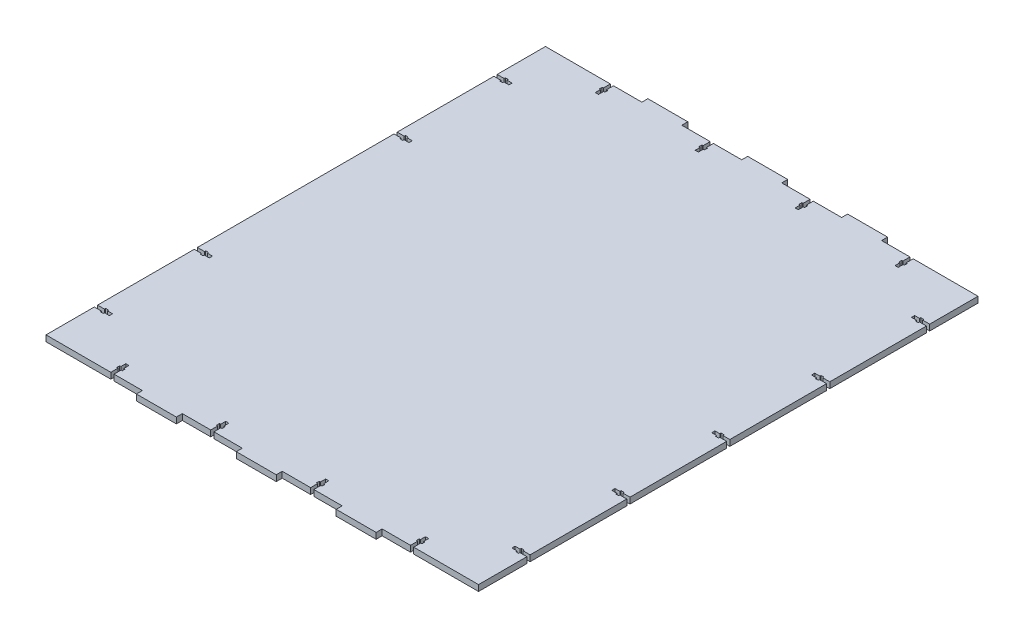
SolidWorks part; units mm, degrees
ref_plane "Front Plane" through (0, 0, 0) normal (0, 0, 1) x (1, 0, 0)
ref_plane "Top Plane" through (0, 0, 0) normal (0, 1, 0) x (1, 0, 0)
ref_plane "Right Plane" through (0, 0, 0) normal (1, 0, 0) x (0, 0, -1)
sketch "Sketch1" plane through (0, 0, 0) normal (0, 1, 0) x (1, 0, 0)
  line L1 (-216.5, -250) -> (216.5, -250)
  line L2 (-216.5, -250) -> (-216.5, 250)
  line L3 (-216.5, 250) -> (216.5, 250)
  line L4 (216.5, -250) -> (216.5, 250)
  line L5 (-216.5, -250) -> (216.5, 250) construction
  line L6 (-216.5, 250) -> (216.5, -250) construction
  point P0 (0, 0)
  dimension "D1" = 433
  dimension "D2" = 500
extrude "Boss-Extrude1" add sketch "Sketch1" along normal blind 6
sketch "Sketch2" plane through (0, 0, 0) normal (0, -1, 0) x (1, 0, 0)
  line L14 (0, 0) -> (0, 133.2527) construction
  line L15 (0, 0) -> (-145.1849, 0) construction
  line L40 (-148.4, 256) -> (-151.6, 256) construction
  line L41 (-148.4, 256) -> (-151.6, 256) construction
  line L42 (-48.4, 256) -> (-51.6, 256) construction
  line L43 (-48.4, 256) -> (-51.6, 256) construction
  line L44 (-148.4, 256) -> (-51.6, 256) construction
  line L45 (-216.5, 250) -> (216.5, 250) construction
  line L46 (-120, 256) -> (-80, 256)
  line L47 (-120, 256) -> (-120, 250)
  line L48 (-120, 250) -> (-80, 250)
  line L49 (-80, 256) -> (-80, 250)
  line L50 (-20, 250) -> (20, 250)
  line L51 (20, 256) -> (20, 250)
  line L52 (-20, 256) -> (20, 256)
  line L53 (-20, 256) -> (-20, 250)
  line L54 (80, 250) -> (120, 250)
  line L55 (120, 256) -> (120, 250)
  line L56 (80, 256) -> (120, 256)
  line L57 (80, 256) -> (80, 250)
  line L58 (120, -256) -> (120, -250)
  line L59 (80, -250) -> (120, -250)
  line L60 (80, -256) -> (120, -256)
  line L61 (80, -256) -> (80, -250)
  line L62 (20, -256) -> (20, -250)
  line L63 (-20, -256) -> (20, -256)
  line L64 (-20, -250) -> (20, -250)
  line L65 (-20, -256) -> (-20, -250)
  line L66 (-120, -250) -> (-80, -250)
  line L67 (-120, -256) -> (-120, -250)
  line L68 (-120, -256) -> (-80, -256)
  line L69 (-80, -256) -> (-80, -250)
  point P50 (-100, 256)
  dimension "D3" = 40
  dimension "D4" = 3
extrude "Boss-Extrude2" add sketch "Sketch2" against normal blind 6
sketch "Sketch3" plane through (0, 0, 0) normal (0, -1, 0) x (1, 0, 0)
  line L0 (-222.5, -198.4) -> (-222.5, -201.6) construction
  line L1 (-222.5, -198.4) -> (-222.5, -201.6)
  line L2 (-222.5, -200) -> (-193.4637, -200) construction
  line L3 (-216.5, -250) -> (-216.5, 250) construction
  line L4 (-201.5, -201.6) -> (-206.5, -201.6)
  line L5 (-201.5, -201.6) -> (-201.5, -198.4)
  line L6 (-201.5, -198.4) -> (-206.5, -198.4)
  line L7 (-216.5, -201.6) -> (-216.5, -198.4)
  line L8 (-201.5, -201.6) -> (-216.5, -198.4) construction
  line L9 (-201.5, -198.4) -> (-216.5, -201.6) construction
  line L10 (-209.5, -198.4) -> (-216.5, -198.4)
  line L11 (-206.5, -202.8) -> (-209.5, -202.8)
  line L12 (-206.5, -202.8) -> (-206.5, -201.6)
  line L13 (-206.5, -197.2) -> (-209.5, -197.2)
  line L14 (-209.5, -202.8) -> (-209.5, -201.6)
  line L15 (-206.5, -202.8) -> (-209.5, -197.2) construction
  line L16 (-206.5, -197.2) -> (-209.5, -202.8) construction
  line L17 (-209.5, -201.6) -> (-216.5, -201.6)
  line L18 (-201.5, -101.6) -> (-206.5, -101.6)
  line L19 (-209.5, -198.4) -> (-209.5, -197.2)
  line L20 (-206.5, -198.4) -> (-206.5, -197.2)
  line L21 (206.5, 202.8) -> (209.5, 197.2) construction
  line L22 (-201.5, -101.6) -> (-201.5, -98.4)
  line L24 (-201.5, -98.4) -> (-206.5, -98.4)
  line L25 (-216.5, -101.6) -> (-216.5, -98.4)
  line L26 (-209.5, -98.4) -> (-216.5, -98.4)
  line L27 (-206.5, -102.8) -> (-209.5, -102.8)
  line L28 (-206.5, -102.8) -> (-206.5, -101.6)
  line L29 (-206.5, -97.2) -> (-209.5, -97.2)
  line L30 (-209.5, -102.8) -> (-209.5, -101.6)
  line L31 (-209.5, -101.6) -> (-216.5, -101.6)
  line L32 (-209.5, -98.4) -> (-209.5, -97.2)
  line L33 (-206.5, -98.4) -> (-206.5, -97.2)
  line L34 (-201.5, -101.6) -> (-216.5, -98.4) construction
  line L35 (-201.5, -98.4) -> (-216.5, -101.6) construction
  line L36 (-206.5, -102.8) -> (-209.5, -97.2) construction
  line L37 (-206.5, -97.2) -> (-209.5, -102.8) construction
  line L38 (-201.5, -1.6) -> (-206.5, -1.6)
  line L39 (-201.5, -1.6) -> (-201.5, 1.6)
  line L40 (-201.5, 1.6) -> (-206.5, 1.6)
  line L41 (-216.5, -1.6) -> (-216.5, 1.6)
  line L42 (-209.5, 1.6) -> (-216.5, 1.6)
  line L43 (-206.5, -2.8) -> (-209.5, -2.8)
  line L44 (-206.5, -2.8) -> (-206.5, -1.6)
  line L45 (-206.5, 2.8) -> (-209.5, 2.8)
  line L46 (-209.5, -2.8) -> (-209.5, -1.6)
  line L47 (-209.5, -1.6) -> (-216.5, -1.6)
  line L48 (-209.5, 1.6) -> (-209.5, 2.8)
  line L49 (-206.5, 1.6) -> (-206.5, 2.8)
  line L50 (-201.5, -1.6) -> (-216.5, 1.6) construction
  line L51 (-201.5, 1.6) -> (-216.5, -1.6) construction
  line L52 (-206.5, -2.8) -> (-209.5, 2.8) construction
  line L53 (-206.5, 2.8) -> (-209.5, -2.8) construction
  line L54 (-201.5, 98.4) -> (-206.5, 98.4)
  line L55 (-201.5, 98.4) -> (-201.5, 101.6)
  line L56 (-201.5, 101.6) -> (-206.5, 101.6)
  line L57 (-216.5, 98.4) -> (-216.5, 101.6)
  line L58 (-209.5, 101.6) -> (-216.5, 101.6)
  line L59 (-206.5, 97.2) -> (-209.5, 97.2)
  line L60 (-206.5, 97.2) -> (-206.5, 98.4)
  line L61 (-206.5, 102.8) -> (-209.5, 102.8)
  line L62 (-209.5, 97.2) -> (-209.5, 98.4)
  line L63 (-209.5, 98.4) -> (-216.5, 98.4)
  line L64 (-209.5, 101.6) -> (-209.5, 102.8)
  line L65 (-206.5, 101.6) -> (-206.5, 102.8)
  line L66 (-201.5, 98.4) -> (-216.5, 101.6) construction
  line L67 (-201.5, 101.6) -> (-216.5, 98.4) construction
  line L68 (-206.5, 97.2) -> (-209.5, 102.8) construction
  line L69 (-206.5, 102.8) -> (-209.5, 97.2) construction
  line L70 (-201.5, 198.4) -> (-206.5, 198.4)
  line L71 (-201.5, 198.4) -> (-201.5, 201.6)
  line L72 (-201.5, 201.6) -> (-206.5, 201.6)
  line L73 (-216.5, 198.4) -> (-216.5, 201.6)
  line L74 (-209.5, 201.6) -> (-216.5, 201.6)
  line L75 (-206.5, 197.2) -> (-209.5, 197.2)
  line L76 (-206.5, 197.2) -> (-206.5, 198.4)
  line L77 (-206.5, 202.8) -> (-209.5, 202.8)
  line L78 (-209.5, 197.2) -> (-209.5, 198.4)
  line L79 (-209.5, 198.4) -> (-216.5, 198.4)
  line L80 (-209.5, 201.6) -> (-209.5, 202.8)
  line L81 (-206.5, 201.6) -> (-206.5, 202.8)
  line L82 (-201.5, 198.4) -> (-216.5, 201.6) construction
  line L83 (-201.5, 201.6) -> (-216.5, 198.4) construction
  line L84 (-206.5, 197.2) -> (-209.5, 202.8) construction
  line L85 (-206.5, 202.8) -> (-209.5, 197.2) construction
  line L86 (0, 0) -> (0, 128.8409) construction
  line L87 (206.5, 197.2) -> (209.5, 202.8) construction
  line L88 (201.5, 201.6) -> (216.5, 198.4) construction
  line L89 (201.5, 198.4) -> (216.5, 201.6) construction
  line L90 (206.5, 102.8) -> (209.5, 97.2) construction
  line L91 (206.5, 97.2) -> (209.5, 102.8) construction
  line L92 (201.5, 101.6) -> (216.5, 98.4) construction
  line L93 (201.5, 98.4) -> (216.5, 101.6) construction
  line L94 (206.5, 2.8) -> (209.5, -2.8) construction
  line L95 (206.5, -2.8) -> (209.5, 2.8) construction
  line L96 (201.5, 1.6) -> (216.5, -1.6) construction
  line L97 (201.5, -1.6) -> (216.5, 1.6) construction
  line L98 (206.5, -97.2) -> (209.5, -102.8) construction
  line L99 (206.5, -102.8) -> (209.5, -97.2) construction
  line L100 (201.5, -98.4) -> (216.5, -101.6) construction
  line L101 (201.5, -101.6) -> (216.5, -98.4) construction
  line L102 (206.5, -197.2) -> (209.5, -202.8) construction
  line L103 (206.5, -202.8) -> (209.5, -197.2) construction
  line L104 (201.5, -198.4) -> (216.5, -201.6) construction
  line L105 (201.5, -201.6) -> (216.5, -198.4) construction
  line L106 (206.5, 201.6) -> (206.5, 202.8)
  line L107 (209.5, 201.6) -> (209.5, 202.8)
  line L108 (209.5, 198.4) -> (216.5, 198.4)
  line L109 (209.5, 197.2) -> (209.5, 198.4)
  line L110 (206.5, 202.8) -> (209.5, 202.8)
  line L111 (206.5, 197.2) -> (206.5, 198.4)
  line L112 (206.5, 197.2) -> (209.5, 197.2)
  line L113 (209.5, 201.6) -> (216.5, 201.6)
  line L114 (216.5, 198.4) -> (216.5, 201.6)
  line L115 (201.5, 201.6) -> (206.5, 201.6)
  line L116 (201.5, 198.4) -> (201.5, 201.6)
  line L117 (201.5, 198.4) -> (206.5, 198.4)
  line L118 (206.5, 101.6) -> (206.5, 102.8)
  line L119 (209.5, 101.6) -> (209.5, 102.8)
  line L120 (209.5, 98.4) -> (216.5, 98.4)
  line L121 (209.5, 97.2) -> (209.5, 98.4)
  line L122 (206.5, 102.8) -> (209.5, 102.8)
  line L123 (206.5, 97.2) -> (206.5, 98.4)
  line L124 (206.5, 97.2) -> (209.5, 97.2)
  line L125 (209.5, 101.6) -> (216.5, 101.6)
  line L126 (216.5, 98.4) -> (216.5, 101.6)
  line L127 (201.5, 101.6) -> (206.5, 101.6)
  line L128 (201.5, 98.4) -> (201.5, 101.6)
  line L129 (201.5, 98.4) -> (206.5, 98.4)
  line L130 (206.5, 1.6) -> (206.5, 2.8)
  line L131 (209.5, 1.6) -> (209.5, 2.8)
  line L132 (209.5, -1.6) -> (216.5, -1.6)
  line L133 (209.5, -2.8) -> (209.5, -1.6)
  line L134 (206.5, 2.8) -> (209.5, 2.8)
  line L135 (206.5, -2.8) -> (206.5, -1.6)
  line L136 (206.5, -2.8) -> (209.5, -2.8)
  line L137 (209.5, 1.6) -> (216.5, 1.6)
  line L138 (216.5, -1.6) -> (216.5, 1.6)
  line L139 (201.5, 1.6) -> (206.5, 1.6)
  line L140 (201.5, -1.6) -> (201.5, 1.6)
  line L141 (201.5, -1.6) -> (206.5, -1.6)
  line L142 (206.5, -98.4) -> (206.5, -97.2)
  line L143 (209.5, -98.4) -> (209.5, -97.2)
  line L144 (209.5, -101.6) -> (216.5, -101.6)
  line L145 (209.5, -102.8) -> (209.5, -101.6)
  line L146 (206.5, -97.2) -> (209.5, -97.2)
  line L147 (206.5, -102.8) -> (206.5, -101.6)
  line L148 (206.5, -102.8) -> (209.5, -102.8)
  line L149 (209.5, -98.4) -> (216.5, -98.4)
  line L150 (216.5, -101.6) -> (216.5, -98.4)
  line L151 (201.5, -98.4) -> (206.5, -98.4)
  line L152 (201.5, -101.6) -> (201.5, -98.4)
  line L153 (206.5, -198.4) -> (206.5, -197.2)
  line L154 (209.5, -198.4) -> (209.5, -197.2)
  line L155 (201.5, -101.6) -> (206.5, -101.6)
  line L156 (209.5, -201.6) -> (216.5, -201.6)
  line L157 (209.5, -202.8) -> (209.5, -201.6)
  line L158 (206.5, -197.2) -> (209.5, -197.2)
  line L159 (206.5, -202.8) -> (206.5, -201.6)
  line L160 (206.5, -202.8) -> (209.5, -202.8)
  line L161 (209.5, -198.4) -> (216.5, -198.4)
  line L162 (216.5, -201.6) -> (216.5, -198.4)
  line L163 (201.5, -198.4) -> (206.5, -198.4)
  line L164 (201.5, -201.6) -> (201.5, -198.4)
  line L165 (201.5, -201.6) -> (206.5, -201.6)
  line L166 (-151.6, -256) -> (-148.4, -256) construction
  line L167 (-151.6, -256) -> (-148.4, -256) construction
  line L168 (-150, -256) -> (-150, -234.6121) construction
  line L169 (-120, -250) -> (-216.5, -250) construction
  line L170 (-151.6, -235) -> (-148.4, -235)
  line L171 (-151.6, -235) -> (-151.6, -240)
  line L172 (-151.6, -250) -> (-148.4, -250)
  line L173 (-148.4, -235) -> (-148.4, -240)
  line L174 (-151.6, -235) -> (-148.4, -250) construction
  line L175 (-151.6, -250) -> (-148.4, -235) construction
  line L176 (-148.4, -243) -> (-147.2, -243)
  line L177 (-152.8, -243) -> (-151.6, -243)
  line L178 (-152.8, -243) -> (-152.8, -240)
  line L179 (-152.8, -240) -> (-151.6, -240)
  line L180 (-147.2, -243) -> (-147.2, -240)
  line L181 (-152.8, -243) -> (-147.2, -240) construction
  line L182 (-152.8, -240) -> (-147.2, -243) construction
  line L183 (-151.6, -243) -> (-151.6, -250)
  line L184 (-148.4, -243) -> (-148.4, -250)
  line L185 (-148.4, -240) -> (-147.2, -240)
  line L186 (-51.6, -235) -> (-48.4, -235)
  line L187 (-51.6, -235) -> (-51.6, -240)
  line L188 (-51.6, -250) -> (-48.4, -250)
  line L189 (-48.4, -235) -> (-48.4, -240)
  line L190 (-48.4, -243) -> (-47.2, -243)
  line L191 (-52.8, -243) -> (-51.6, -243)
  line L192 (-52.8, -243) -> (-52.8, -240)
  line L193 (-52.8, -240) -> (-51.6, -240)
  line L194 (-47.2, -243) -> (-47.2, -240)
  line L195 (-51.6, -243) -> (-51.6, -250)
  line L196 (-48.4, -243) -> (-48.4, -250)
  line L197 (-48.4, -240) -> (-47.2, -240)
  line L198 (-51.6, -235) -> (-48.4, -250) construction
  line L199 (-51.6, -250) -> (-48.4, -235) construction
  line L200 (-52.8, -243) -> (-47.2, -240) construction
  line L201 (-52.8, -240) -> (-47.2, -243) construction
  line L202 (48.4, -235) -> (51.6, -235)
  line L203 (48.4, -235) -> (48.4, -240)
  line L204 (48.4, -250) -> (51.6, -250)
  line L205 (51.6, -235) -> (51.6, -240)
  line L206 (51.6, -243) -> (52.8, -243)
  line L207 (47.2, -243) -> (48.4, -243)
  line L208 (47.2, -243) -> (47.2, -240)
  line L209 (47.2, -240) -> (48.4, -240)
  line L210 (52.8, -243) -> (52.8, -240)
  line L211 (48.4, -243) -> (48.4, -250)
  line L212 (51.6, -243) -> (51.6, -250)
  line L213 (51.6, -240) -> (52.8, -240)
  line L214 (48.4, -235) -> (51.6, -250) construction
  line L215 (48.4, -250) -> (51.6, -235) construction
  line L216 (47.2, -243) -> (52.8, -240) construction
  line L217 (47.2, -240) -> (52.8, -243) construction
  line L218 (148.4, -235) -> (151.6, -235)
  line L219 (148.4, -235) -> (148.4, -240)
  line L220 (148.4, -250) -> (151.6, -250)
  line L221 (151.6, -235) -> (151.6, -240)
  line L222 (151.6, -243) -> (152.8, -243)
  line L223 (147.2, -243) -> (148.4, -243)
  line L224 (147.2, -243) -> (147.2, -240)
  line L225 (147.2, -240) -> (148.4, -240)
  line L226 (152.8, -243) -> (152.8, -240)
  line L227 (148.4, -243) -> (148.4, -250)
  line L228 (151.6, -243) -> (151.6, -250)
  line L229 (151.6, -240) -> (152.8, -240)
  line L230 (148.4, -235) -> (151.6, -250) construction
  line L231 (148.4, -250) -> (151.6, -235) construction
  line L232 (147.2, -243) -> (152.8, -240) construction
  line L233 (147.2, -240) -> (152.8, -243) construction
  line L234 (0, 0) -> (96.8105, 0) construction
  line L235 (147.2, 240) -> (152.8, 243) construction
  line L236 (147.2, 243) -> (152.8, 240) construction
  line L237 (148.4, 250) -> (151.6, 235) construction
  line L238 (148.4, 235) -> (151.6, 250) construction
  line L239 (47.2, 240) -> (52.8, 243) construction
  line L240 (47.2, 243) -> (52.8, 240) construction
  line L241 (48.4, 250) -> (51.6, 235) construction
  line L242 (48.4, 235) -> (51.6, 250) construction
  line L243 (-52.8, 240) -> (-47.2, 243) construction
  line L244 (-52.8, 243) -> (-47.2, 240) construction
  line L245 (-51.6, 250) -> (-48.4, 235) construction
  line L246 (-51.6, 235) -> (-48.4, 250) construction
  line L247 (-152.8, 240) -> (-147.2, 243) construction
  line L248 (-152.8, 243) -> (-147.2, 240) construction
  line L249 (-151.6, 250) -> (-148.4, 235) construction
  line L250 (-151.6, 235) -> (-148.4, 250) construction
  line L251 (151.6, 240) -> (152.8, 240)
  line L252 (151.6, 243) -> (151.6, 250)
  line L253 (148.4, 243) -> (148.4, 250)
  line L254 (152.8, 243) -> (152.8, 240)
  line L255 (147.2, 240) -> (148.4, 240)
  line L256 (147.2, 243) -> (147.2, 240)
  line L257 (147.2, 243) -> (148.4, 243)
  line L258 (151.6, 243) -> (152.8, 243)
  line L259 (151.6, 235) -> (151.6, 240)
  line L260 (148.4, 250) -> (151.6, 250)
  line L261 (148.4, 235) -> (148.4, 240)
  line L262 (148.4, 235) -> (151.6, 235)
  line L263 (51.6, 240) -> (52.8, 240)
  line L264 (51.6, 243) -> (51.6, 250)
  line L265 (48.4, 243) -> (48.4, 250)
  line L266 (52.8, 243) -> (52.8, 240)
  line L267 (47.2, 240) -> (48.4, 240)
  line L268 (47.2, 243) -> (47.2, 240)
  line L269 (47.2, 243) -> (48.4, 243)
  line L270 (51.6, 243) -> (52.8, 243)
  line L271 (51.6, 235) -> (51.6, 240)
  line L272 (48.4, 250) -> (51.6, 250)
  line L273 (48.4, 235) -> (48.4, 240)
  line L274 (48.4, 235) -> (51.6, 235)
  line L275 (-48.4, 240) -> (-47.2, 240)
  line L276 (-48.4, 243) -> (-48.4, 250)
  line L277 (-51.6, 243) -> (-51.6, 250)
  line L278 (-47.2, 243) -> (-47.2, 240)
  line L279 (-52.8, 240) -> (-51.6, 240)
  line L280 (-52.8, 243) -> (-52.8, 240)
  line L281 (-52.8, 243) -> (-51.6, 243)
  line L282 (-48.4, 243) -> (-47.2, 243)
  line L283 (-48.4, 235) -> (-48.4, 240)
  line L284 (-51.6, 250) -> (-48.4, 250)
  line L285 (-51.6, 235) -> (-51.6, 240)
  line L286 (-51.6, 235) -> (-48.4, 235)
  line L287 (-148.4, 240) -> (-147.2, 240)
  line L288 (-148.4, 243) -> (-148.4, 250)
  line L289 (-151.6, 243) -> (-151.6, 250)
  line L290 (-147.2, 243) -> (-147.2, 240)
  line L291 (-152.8, 240) -> (-151.6, 240)
  line L292 (-152.8, 243) -> (-152.8, 240)
  line L293 (-152.8, 243) -> (-151.6, 243)
  line L294 (-148.4, 243) -> (-147.2, 243)
  line L295 (-148.4, 235) -> (-148.4, 240)
  line L296 (-151.6, 250) -> (-148.4, 250)
  line L297 (-151.6, 235) -> (-151.6, 240)
  line L298 (-151.6, 235) -> (-148.4, 235)
  point P4 (-209, -200)
  point P11 (-208, -200)
  point P25 (-209, -100)
  point P31 (-208, -100)
  point P40 (-209, 0)
  point P45 (-208, 0)
  point P54 (-209, 100)
  point P59 (-208, 100)
  point P68 (-209, 200)
  point P73 (-208, 200)
  point P140 (208, 200)
  point P141 (209, 200)
  point P142 (208, 100)
  point P143 (209, 100)
  point P144 (208, 0)
  point P145 (209, 0)
  point P146 (208, -100)
  point P147 (209, -100)
  point P148 (208, -200)
  point P149 (209, -200)
  point P154 (-150, -242.5)
  point P161 (-150, -241.5)
  point P171 (-50, -242.5)
  point P176 (-50, -241.5)
  point P185 (50, -242.5)
  point P190 (50, -241.5)
  point P199 (150, -242.5)
  point P204 (150, -241.5)
  point P261 (150, 241.5)
  point P262 (150, 242.5)
  point P263 (50, 241.5)
  point P264 (50, 242.5)
  point P265 (-50, 241.5)
  point P266 (-50, 242.5)
  point P267 (-150, 241.5)
  point P268 (-150, 242.5)
  line M5 (216.5, -250) -> (216.5, 250)
  line M6 (216.5, 250) -> (120, 250)
  line M10 (80, 250) -> (20, 250)
  line M14 (-20, 250) -> (-80, 250)
  line M18 (-120, 250) -> (-216.5, 250)
  line M19 (-216.5, 250) -> (-216.5, -250)
  line M20 (-216.5, -250) -> (-120, -250)
  line M24 (-80, -250) -> (-20, -250)
  line M28 (20, -250) -> (80, -250)
  line M32 (120, -250) -> (216.5, -250)
  dimension "D1" = 15
  dimension "D2" = 3
  dimension "D3" = 7
  dimension "D4" = 5.6
  dimension "D5" = 5
  dimension "D6" = 15
  dimension "D7" = 5.6
  dimension "D8" = 7
  dimension "D9" = 4
extrude "Cut-Extrude1" cut sketch "Sketch3" against normal through all contours L297 L298 L295 L287 L290 L294 L288 L289 L293 L292 L291 M18 | L285 L286 L283 L275 L278 L282 L276 L277 L281 L280 L279 M14 | L261 L262 L259 L251 L254 L258 L252 L253 L257 L256 L255 M6 | L116 L117 L111 L112 L109 L108 L113 L107 L110 L106 L115 M5 | L128 L129 L123 L124 L121 L120 L125 L119 L122 L118 L127 M5 | L140 L141 L135 L136 L133 L132 L137 L131 L134 L130 L139 M5 | L152 L155 L147 L148 L145 L144 L149 L143 L146 L142 L151 M5 | L164 L165 L159 L160 L157 L156 L161 L154 L158 L153 L163 M5 | L229 L221 L218 L219 L225 L224 L223 L227 L228 L222 L226 M32 | L213 L205 L202 L203 L209 L208 L207 L211 L212 L206 L210 M28 | L197 L189 L186 L187 L193 L192 L191 L195 L196 L190 L194 M24 | L185 L173 L170 L171 L179 L178 L177 L183 L184 L176 L180 M20 | L6 L20 L13 L19 L10 L17 L14 L11 L12 L4 L5 M19 | L24 L33 L29 L32 L26 L31 L30 L27 L28 L18 L22 M19 | L72 L81 L77 L80 L74 L79 L78 L75 L76 L70 L71 M19 | L273 L274 L271 L263 L266 L270 L264 L265 L269 L268 L267 M10 | L56 L65 L61 L64 L58 L57 L63 L62 L59 L60 L54 L55 region at (-150, 0, -242.3696) region at (-150, 0, 242.3696) region at (-208.8696, 0, 200) region at (-208.8696, 0, -100) region at (-208.8696, 0, -200) region at (150, 0, 242.3696) region at (150, 0, -242.3696) region at (208.8696, 0, -200) region at (208.8696, 0, -100) region at (208.8696, 0, 0) region at (208.8696, 0, 100) region at (208.8696, 0, 200) region at (-50, 0, -242.3696) region at (50, 0, -242.3696) region at (50, 0, 242.3696) region at (-50, 0, 242.3696)
